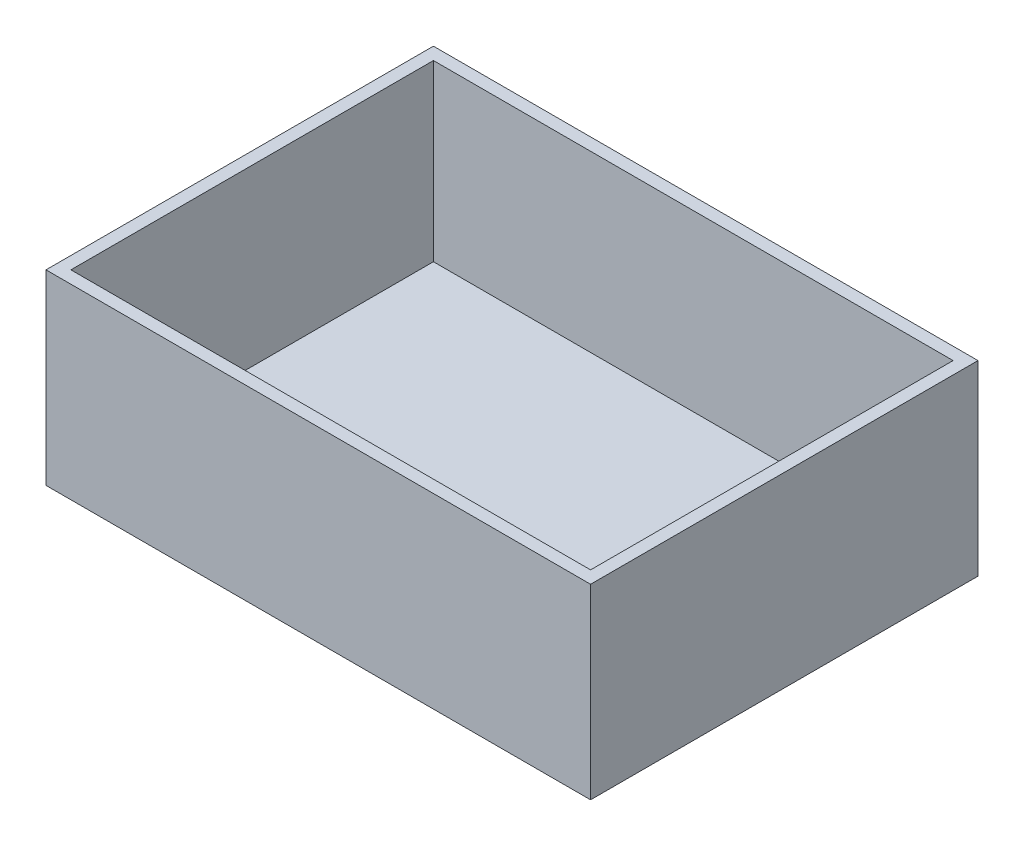
SolidWorks part; units mm, degrees
ref_plane "Alzado" through (0, 0, 0) normal (0, 0, 1) x (1, 0, 0)
ref_plane "Planta" through (0, 0, 0) normal (0, 1, 0) x (1, 0, 0)
ref_plane "Vista lateral" through (0, 0, 0) normal (1, 0, 0) x (0, 0, -1)
sketch "Croquis1" plane through (0, 0, 0) normal (0, 1, 0) x (1, 0, 0)
  line L1 (43.75, -31.125) -> (-43.75, -31.125)
  line L2 (43.75, -31.125) -> (43.75, 31.125)
  line L3 (43.75, 31.125) -> (-43.75, 31.125)
  line L4 (-43.75, -31.125) -> (-43.75, 31.125)
  line L5 (43.75, -31.125) -> (-43.75, 31.125) construction
  line L6 (43.75, 31.125) -> (-43.75, -31.125) construction
  point P0 (0, 0)
  dimension "D1" = 87.5
  dimension "D2" = 62.25
extrude "Saliente-Extruir1" add sketch "Croquis1" along normal blind 30
shell "Vaciado1" thickness 2 removed face at (0, 30, 0)
